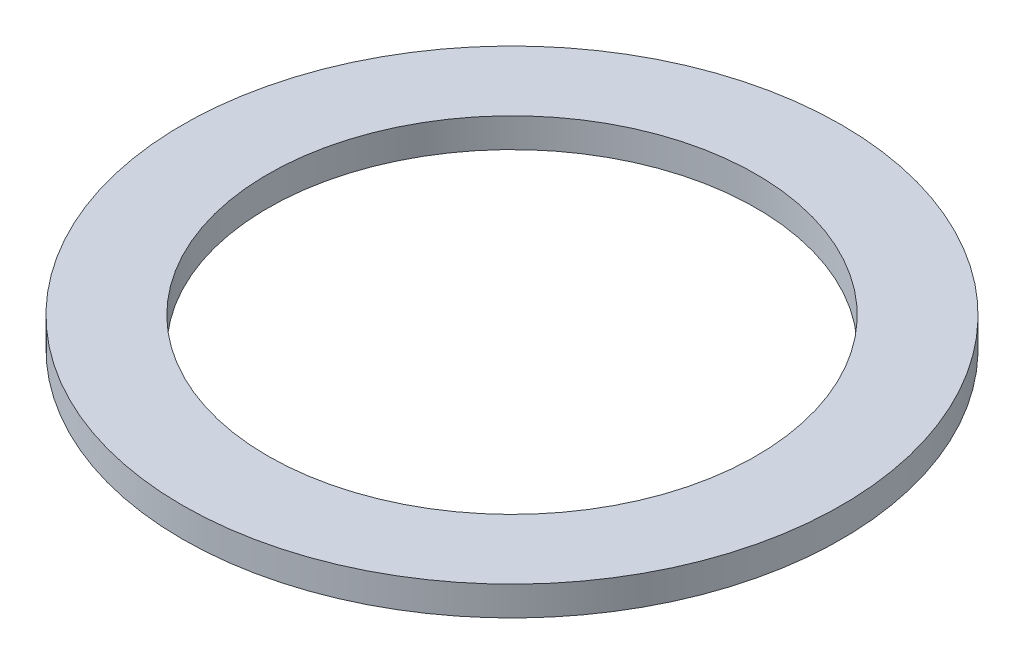
SolidWorks part; units mm, degrees
ref_plane "Front Plane" through (0, 0, 0) normal (0, 0, 1) x (1, 0, 0)
ref_plane "Top Plane" through (0, 0, 0) normal (0, 1, 0) x (1, 0, 0)
ref_plane "Right Plane" through (0, 0, 0) normal (1, 0, 0) x (0, 0, -1)
sketch "Sketch1" plane through (0, 0, 0) normal (0, 1, 0) x (1, 0, 0)
  circle A0 centre (0, 0) radius 67.5
  dimension "FLANGE_OD" = 135
extrude "Boss-Extrude1" add sketch "Sketch1" along normal blind 6
sketch "Sketch2" plane through (0, 0, 0) normal (0, 1, 0) x (1, 0, 0)
  circle A0 centre (0, 0) radius 50
  dimension "BORE_D" = 100
extrude "Cut-Extrude1" cut sketch "Sketch2" along normal through all
sketch "Sketch3" plane through (0, 6, 0) normal (0, 1, 0) x (1, 0, 0)
  circle A0 centre (0, 0) radius 29.9798 construction
  circle A1 centre (-29.9798, 0) radius 2.1246
  dimension "BOLT_D" = 4.2492
  dimension "BOLT_PCD" = 59.9595
extrude "Cut-Extrude2" cut sketch "Sketch3" against normal blind 5.3291 rebuild error yes
pattern_circular "CirPattern1" count 4 over 360 rebuild error yes
